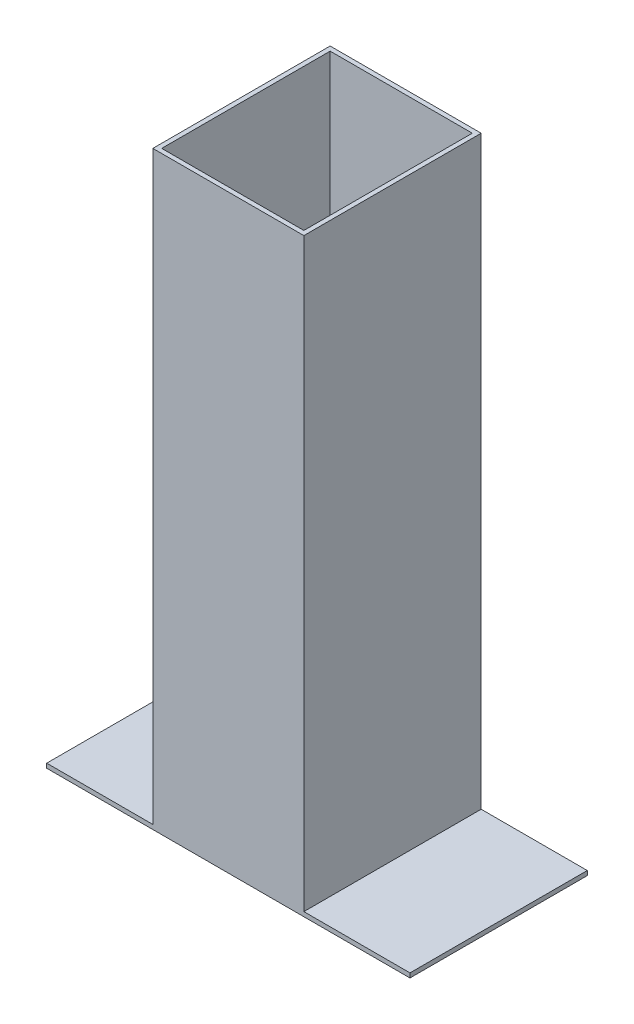
SolidWorks part; units mm, degrees
ref_plane "Front Plane" through (0, 0, 0) normal (0, 0, 1) x (1, 0, 0)
ref_plane "Top Plane" through (0, 0, 0) normal (0, 1, 0) x (1, 0, 0)
ref_plane "Right Plane" through (0, 0, 0) normal (1, 0, 0) x (0, 0, -1)
sketch "Sketch2" plane through (0, 0, 0) normal (0, 0, 1) x (1, 0, 0)
  line L0 (-577.7442, 0) -> (577.7442, 0) construction
  line L1 (0, -368.7209) -> (0, 368.7209) construction
  line L2 (-108.175, 0) -> (108.175, 0)
  line L3 (108.175, 6.35) -> (108.175, 845)
  line L4 (108.175, 845) -> (-108.175, 845)
  line L5 (-108.175, 6.35) -> (-108.175, 845)
  line L6 (101.825, 838.65) -> (-101.825, 838.65) construction
  line L7 (-101.825, 6.35) -> (-101.825, 838.65) construction
  line L8 (-101.825, 6.35) -> (101.825, 6.35) construction
  line L9 (101.825, 6.35) -> (101.825, 838.65) construction
  line L10 (108.175, 6.35) -> (260.175, 6.35)
  line L11 (260.175, 6.35) -> (260.175, 0)
  line L12 (260.175, 0) -> (108.175, 0)
  line L13 (-260.175, 6.35) -> (-260.175, 0)
  line L14 (-260.175, 0) -> (-108.175, 0)
  line L15 (-108.175, 6.35) -> (-260.175, 6.35)
  line L17 (108.175, 0) -> (108.175, 845) construction
  line L18 (-108.175, 0) -> (-108.175, 845) construction
  point P4 (0, 0)
  point P8 (0, 0)
  point P13 (0, 0)
  point P14 (0, 845)
  dimension "D1" = 108.175
  dimension "D2" = 845
  dimension "D3" = 6.35
  dimension "D4" = 152
extrude "Boss-Extrude1" add sketch "Sketch2" along normal mid plane 254
sketch "Sketch3" plane through (0, 845, 0) normal (0, 1, 0) x (1, 0, 0)
  line L0 (-108.175, 127) -> (108.175, 127) construction
  line L1 (108.175, 127) -> (108.175, -127) construction
  line L2 (108.175, -127) -> (-108.175, -127) construction
  line L3 (-108.175, -127) -> (-108.175, 127) construction
  line L4 (-101.825, 120.65) -> (101.825, 120.65)
  line L5 (101.825, 120.65) -> (101.825, -120.65)
  line L6 (101.825, -120.65) -> (-101.825, -120.65)
  line L7 (-101.825, -120.65) -> (-101.825, 120.65)
  dimension "D1" = 6.35
extrude "Cut-Extrude1" cut sketch "Sketch3" against normal blind 1000
